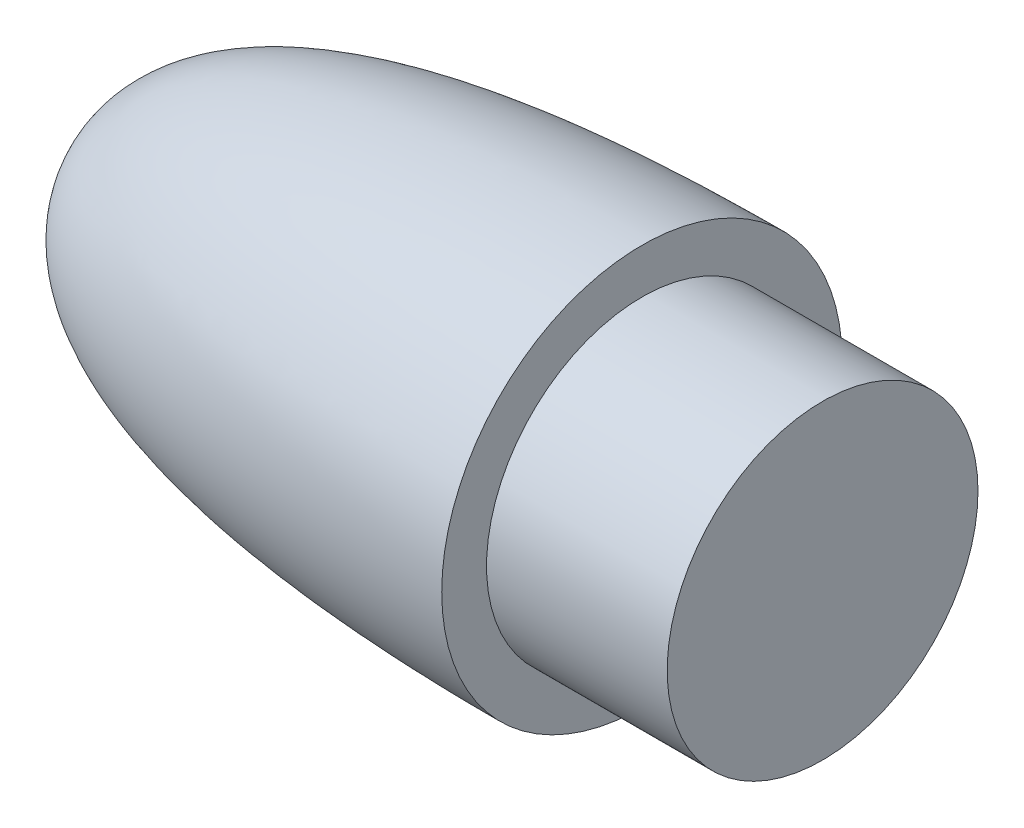
SolidWorks part; units mm, degrees
ref_plane "Front Plane" through (0, 0, 0) normal (0, 0, 1) x (1, 0, 0)
ref_plane "Top Plane" through (0, 0, 0) normal (0, 1, 0) x (1, 0, 0)
ref_plane "Right Plane" through (0, 0, 0) normal (1, 0, 0) x (0, 0, -1)
sketch "Sketch1" plane through (0, 0, 0) normal (0, 1, 0) x (1, 0, 0)
  line L0 (-25.4, 0) -> (-25.4, -6.3)
  line L1 (0, 0) -> (-25.4, 0)
  line L2 (0, 0) -> (0, 43.7)
  line L3 (0, 43.7) -> (-25.4, 43.7)
  line L4 (-25.4, 0) -> (-25.4, 43.7)
  line L5 (-25.4, 43.7) -> (-25.4, 50)
  line L6 (-25.4, 21.85) -> (-101.6, 21.85)
  line L7 (-25.4, -6.3) -> (-101.6, -6.3) construction
  line L8 (-101.6, -6.3) -> (-101.6, 21.85) construction
  line L9 (-25.4, 50) -> (-101.6, 50) construction
  line L10 (-101.6, 50) -> (-101.6, 21.85) construction
  line L11 (-25.4, 21.85) -> (0, 21.85)
  spline S0 degree 2 poles (-25.4, -6.3) (-101.6, -6.3) (-101.6, 21.85) knots 0 0 0 1 1 1
  spline S1 degree 2 poles (-25.4, 50) (-101.6, 50) (-101.6, 21.85) knots 0 0 0 1 1 1
  dimension "D1" = 43.7
  dimension "D2" = 25.4
  dimension "D3" = 6.3
  dimension "D4" = 6.3
  dimension "D5" = 76.2
revolve "Revolve2" add sketch "Sketch1" angle 360 about L6 region at (-58.928, 0, -34.236) region at (-12.7, 0, -32.775)
